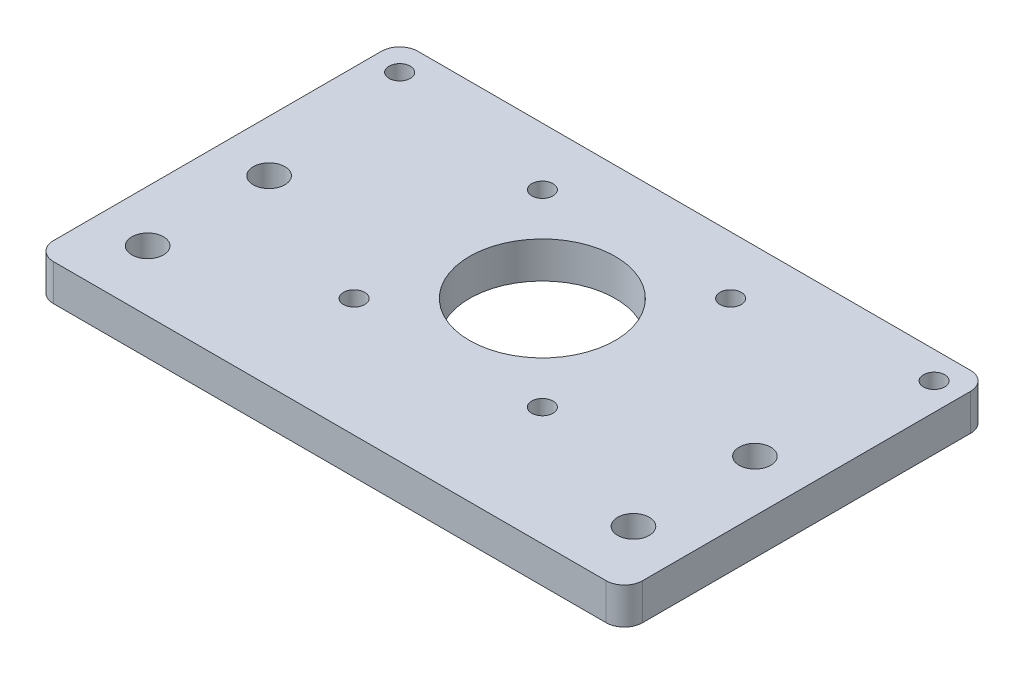
SolidWorks part; units mm, degrees
material "Acrylic (Medium-high impact)"
ref_plane "Front Plane" through (0, 0, 0) normal (0, 0, 1) x (1, 0, 0)
ref_plane "Top Plane" through (0, 0, 0) normal (0, 1, 0) x (1, 0, 0)
ref_plane "Right Plane" through (0, 0, 0) normal (1, 0, 0) x (0, 0, -1)
sketch "Sketch1" plane through (0, 0, 0) normal (0, 1, 0) x (1, 0, 0)
  line L1 (48.5, -30) -> (-48.5, -30)
  line L2 (48.5, -30) -> (48.5, 30)
  line L3 (48.5, 30) -> (-48.5, 30)
  line L4 (-48.5, -30) -> (-48.5, 30)
  line L5 (48.5, -30) -> (-48.5, 30) construction
  line L6 (48.5, 30) -> (-48.5, -30) construction
  point P0 (0, 0)
  dimension "D1" = 97
  dimension "D2" = 60
extrude "Base" add sketch "Sketch1" along normal blind 6
sketch "Sketch2" plane through (0, 6, 0) normal (0, 1, 0) x (1, 0, 0)
  line L1 (0, 5) -> (0, 17.5) construction
  line L2 (-48.5, -30) -> (48.5, -30) construction
  circle A2 centre (0, 5) radius 12
  dimension "D1" = 24
  dimension "D2" = 35
extrude "StepperCaseHole" cut sketch "Sketch2" against normal through all
fillet "FilletEdges3mm" radius 3 4 edges at (48.5, 3, 30) (48.5, 3, -30) (-48.5, 3, -30) (-48.5, 3, 30)
hole_wizard "Ø3.5mm CableTieHoles" positions "Sketch6" profile "Sketch7" hole size "Ø3.5" standard "ISO" end condition through all
sketch "Sketch6" plane through (0, 0, 0) normal (0, -1, 0) x (-1, 0, 0)
  line L0 (-45.5, 30) -> (45.5, 30) construction
  line L1 (-48.5, -27) -> (-48.5, 27) construction
  line L2 (48.5, 27) -> (48.5, -27) construction
  point P0 (-44, 25.5)
  point P2 (44, 25.5)
  point P5 (-36.4438, 23.125)
  point P6 (37.2406, 23.7525)
  point P9 (0, 0)
  dimension "D1" = 4.5
  dimension "D2" = 4.5
  dimension "D3" = 4.5
sketch "Sketch7" plane through (44, 0, -25.5) normal (1, 0, 0) x (0, 0, -1)
  line L0 (0, 0) -> (0, 6)
  line L1 (0, 6) -> (1.75, 6)
  line L2 (1.75, 6) -> (1.75, 0)
  line L5 (1.75, 0) -> (0, 0)
  line L11 (0, -6.35) -> (0, 107.95) construction
  dimension "Thru Hole Dia." = 3.5
  dimension "Thru Hole Depth" = 6
hole_wizard "Ø5.2 (5.2) HolesForCorners" positions "Sketch8" profile "Sketch9" hole size "Ø5.2" standard "ISO" end condition through all
sketch "Sketch8" plane through (0, 6, 0) normal (0, 1, 0) x (1, 0, 0)
  line L0 (0, 0) -> (0, 10.0505) construction
  line L2 (-45.5, -30) -> (45.5, -30) construction
  point P0 (-40, 0)
  point P2 (-40, -20)
  point P4 (40, 0)
  point P6 (40, -20)
  point P18 (0, 0)
  dimension "D1" = 80
  dimension "D2" = 20
  dimension "D3" = 10
sketch "Sketch9" plane through (-40, 6, 0) normal (1, 0, 0) x (0, 0, 1)
  line L0 (0, 0) -> (0, 6)
  line L1 (0, 6) -> (2.6, 6)
  line L2 (2.6, 6) -> (2.6, 0)
  line L5 (2.6, 0) -> (0, 0)
  line L11 (0, -6.35) -> (0, 107.95) construction
  dimension "Thru Hole Dia." = 5.2
  dimension "Thru Hole Depth" = 6
hole_wizard "Ø3.5 (3.5) StepperMountHoles" positions "Sketch10" profile "Sketch11" hole size "Ø3.5" standard "ISO" end condition through all
sketch "Sketch10" plane through (0, 6, 0) normal (0, 1, 0) x (1, 0, 0)
  line L0 (0, 5) -> (-9.0309, 5) construction
  line L2 (0, 12.5358) -> (0, 5) construction
  point P0 (-15.5, 20.5)
  point P2 (-15.5, -10.5)
  point P4 (15.5, -10.5)
  point P6 (15.5, 20.5)
  point P22 (0, 0)
  point P23 (0, 0)
  dimension "D1" = 31
  dimension "D2" = 31
sketch "Sketch11" plane through (-15.5, 6, -20.5) normal (1, 0, 0) x (0, 0, 1)
  line L0 (0, 0) -> (0, 6)
  line L1 (0, 6) -> (1.75, 6)
  line L2 (1.75, 6) -> (1.75, 0)
  line L5 (1.75, 0) -> (0, 0)
  line L11 (0, -6.35) -> (0, 107.95) construction
  dimension "Thru Hole Dia." = 3.5
  dimension "Thru Hole Depth" = 6
